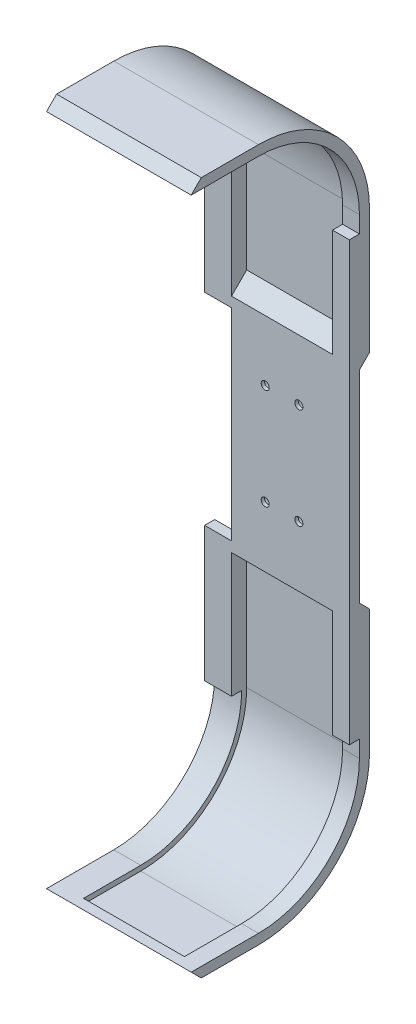
SolidWorks part; units mm, degrees
ref_plane "前视基准面" through (0, 0, 0) normal (0, 0, 1) x (1, 0, 0)
ref_plane "上视基准面" through (0, 0, 0) normal (0, 1, 0) x (1, 0, 0)
ref_plane "右视基准面" through (0, 0, 0) normal (1, 0, 0) x (0, 0, -1)
sketch "草图1" plane through (0, 0, 0) normal (0, 0, 1) x (1, 0, 0)
  line L61 (-143.75, 30) -> (-143.75, 70)
  line L65 (-135.75, 30) -> (-143.75, 30)
  line L80 (-105.75, 65) -> (-105.75, 70)
  line L81 (-143.75, 70) -> (-105.75, 70)
  line L82 (-105.75, 65) -> (-100.25, 65)
  line L83 (-100.25, 65) -> (-100.25, 70)
  line L84 (-100.25, 70) -> (99.75, 70)
  line L85 (-135.75, 30) -> (-135.75, -30)
  line L87 (143.25, -30) -> (143.25, -70)
  line L89 (99.75, 65) -> (99.75, 70)
  line L90 (105.25, 65) -> (99.75, 65)
  line L92 (105.25, 65) -> (105.25, 70)
  line L96 (105.25, -65) -> (105.25, -70)
  line L97 (143.25, -70) -> (105.25, -70)
  line L98 (105.25, -65) -> (99.75, -65)
  line L99 (99.75, -65) -> (99.75, -70)
  line L100 (-100.25, -70) -> (99.75, -70)
  line L101 (-100.25, -65) -> (-100.25, -70)
  line L102 (-105.75, -65) -> (-100.25, -65)
  line L103 (-143.75, -70) -> (-105.75, -70)
  line L104 (-105.75, -65) -> (-105.75, -70)
  line L105 (-135.75, -30) -> (-143.75, -30)
  line L106 (-143.75, -30) -> (-143.75, -70)
  line L107 (143.25, 30) -> (143.25, 70)
  line L108 (105.25, 70) -> (143.25, 70)
  line L109 (143.25, 30) -> (135.25, 30)
  line L110 (135.25, 30) -> (135.25, -30)
  line L111 (135.25, -30) -> (143.25, -30)
  point P9 (-0.25, 70)
  point P27 (-135.75, 0)
  point P35 (0, -70)
extrude "凸台-拉伸1" add sketch "草图1" along normal blind 3
ref_plane "基准面1" through (-143.75, 0, 0) normal (-1, 0, 0) x (0, 0, 1)
sketch "草图2" plane through (-143.75, 0, 0) normal (-1, 0, 0) x (0, 0, 1)
  line L1 (0, 70) -> (0, 30)
  line L2 (0, 30) -> (-3, 33)
  line L3 (-3, 33) -> (-3, 70)
  line L4 (50, 100) -> (47, 103)
  line L8 (30, 103) -> (47, 103)
  line L17 (45, 90) -> (50, 100)
  line L18 (45, 90) -> (60, 90)
  line L19 (60, 90) -> (60, 87)
  line L20 (60, 87) -> (41, 87)
  line L21 (41, 87) -> (47, 100)
  line L22 (30, 100) -> (47, 100)
  line L24 (30, -100) -> (47, -100)
  line L25 (41, -87) -> (47, -100)
  line L26 (60, -87) -> (41, -87)
  line L27 (60, -90) -> (60, -87)
  line L28 (45, -90) -> (60, -90)
  line L29 (45, -90) -> (50, -100)
  line L30 (30, -103) -> (47, -103)
  line L31 (50, -100) -> (47, -103)
  line L32 (-3, -33) -> (-3, -70)
  line L33 (0, -30) -> (-3, -33)
  line L34 (0, -70) -> (0, -30)
  arc A0 (0, 70) -> (30, 100) centre (30, 70) cw
  arc A1 (-3, 70) -> (30, 103) centre (30, 70) cw
  arc A4 (-3, -70) -> (30, -103) centre (30, -70) ccw
  arc A5 (0, -70) -> (30, -100) centre (30, -70) ccw
extrude "凸台-拉伸2" add sketch "草图2" against normal blind 287
sketch "草图4" plane through (-143.75, 0, 0) normal (-1, 0, 0) x (0, 0, 1)
  line L1 (30, 100) -> (47, 100) construction
  line L4 (60.2366, -100) -> (38.5, -100)
  line L5 (60.2366, -100) -> (60.2366, 100)
  line L6 (60.2366, 100) -> (38.5, 100)
  line L7 (38.5, -100) -> (38.5, 100)
extrude "切除-拉伸1" cut sketch "草图4" against normal blind 43
ref_plane "基准面2" through (143.25, 0, 0) normal (1, 0, 0) x (0, 0, -1)
sketch "草图5" plane through (143.25, 0, 0) normal (1, 0, 0) x (0, 0, -1)
  line L1 (-30, 100) -> (-47, 100) construction
  line L4 (-63.1672, -100) -> (-39.752, -100)
  line L5 (-63.1672, -100) -> (-63.1672, 100)
  line L6 (-63.1672, 100) -> (-39.752, 100)
  line L7 (-39.752, -100) -> (-39.752, 100)
extrude "切除-拉伸2" cut sketch "草图5" against normal blind 43
sketch "草图6" plane through (0, 0, 0) normal (0, 0, 1) x (1, 0, 0)
  line L0 (-100.75, 103) -> (203.0936, 103)
  line L3 (143.25, 103) -> (-143.75, 103) construction
  line L7 (-100.75, 103) -> (-100.75, -103)
  line L8 (143.25, -103) -> (-143.75, -103) construction
  line L9 (-100.75, -103) -> (203.0936, -103)
  line L10 (203.0936, -103) -> (203.0936, 103)
extrude "切除-拉伸6" cut sketch "草图6" against normal blind 100 and the other way blind 100
hole_wizard "大小六角凹头盖螺钉柱孔1" positions "草图7" profile "草图8" counterbore size "M2" standard "AS" end condition through all
sketch "草图7" plane through (0, 0, 0) normal (0, 0, -1) x (-1, 0, 0)
  point P18 (115.75, 15)
  point P20 (125.75, 15)
  point P28 (125.75, -15)
  point P32 (115.75, -15)
  point P35 (0, 0)
sketch "草图8" plane through (-115.75, 15, 0) normal (1, 0, 0) x (0, 1, 0)
  line L0 (0, 0) -> (0, 50)
  line L1 (0, 50) -> (1.2, 50)
  line L3 (1.2, 50) -> (1.2, 2)
  line L4 (2.15, 2) -> (1.2, 2)
  line L5 (2.15, 2) -> (2.15, 0.0241)
  line L6 (2.15, 0.0241) -> (2.175, 0)
  line L7 (2.175, 0) -> (0, 0)
  line L8 (-2.15, 0.0241) -> (-2.175, 0) construction
  line L11 (0, -6.35) -> (0, 107.95) construction
  dimension "通孔孔直径" = 2.4
  dimension "通孔孔深度" = 50
  dimension "柱形沉头孔直径" = 4.3
  dimension "柱形沉头孔深度" = 2
  dimension "近端锥形沉头孔直径" = 4.35
  dimension "近端锥形沉头孔角度" = 92
ref_plane "基准面3" through (-135.75, 0, 0) normal (-1, 0, 0) x (0, 0, 1)
sketch "草图10" plane through (-135.75, 0, 0) normal (-1, 0, 0) x (0, 0, 1)
  line L0 (30, 100) -> (47, 100)
  line L1 (30, 100) -> (50, 100) construction
  line L2 (3, 70) -> (0, 70) construction
  line L3 (30, 101.5) -> (45.5, 101.5)
  line L4 (45.5, 101.5) -> (47, 100)
  line L5 (0, 70) -> (3, 70)
  line L6 (3, 70) -> (3, 33)
  line L7 (3, 70) -> (3, 30) construction
  line L8 (3, 33) -> (-1.5, 37.5)
  line L9 (-1.5, 37.5) -> (-1.5, 70)
  line L11 (-1.5, -37.5) -> (-1.5, -70)
  line L12 (3, -33) -> (-1.5, -37.5)
  line L13 (3, -70) -> (3, -33)
  line L14 (0, -70) -> (3, -70)
  line L15 (45.5, -101.5) -> (47, -100)
  line L16 (30, -101.5) -> (45.5, -101.5)
  line L17 (30, -100) -> (47, -100)
  arc A0 (30, 100) -> (0, 70) centre (30, 70) ccw
  arc A1 (30, 101.5) -> (-1.5, 70) centre (30, 70) ccw
  arc A2 (30, -101.5) -> (-1.5, -70) centre (30, -70) cw
  arc A3 (30, -100) -> (0, -70) centre (30, -70) cw
extrude "切除-拉伸7" cut sketch "草图10" against normal blind 30
